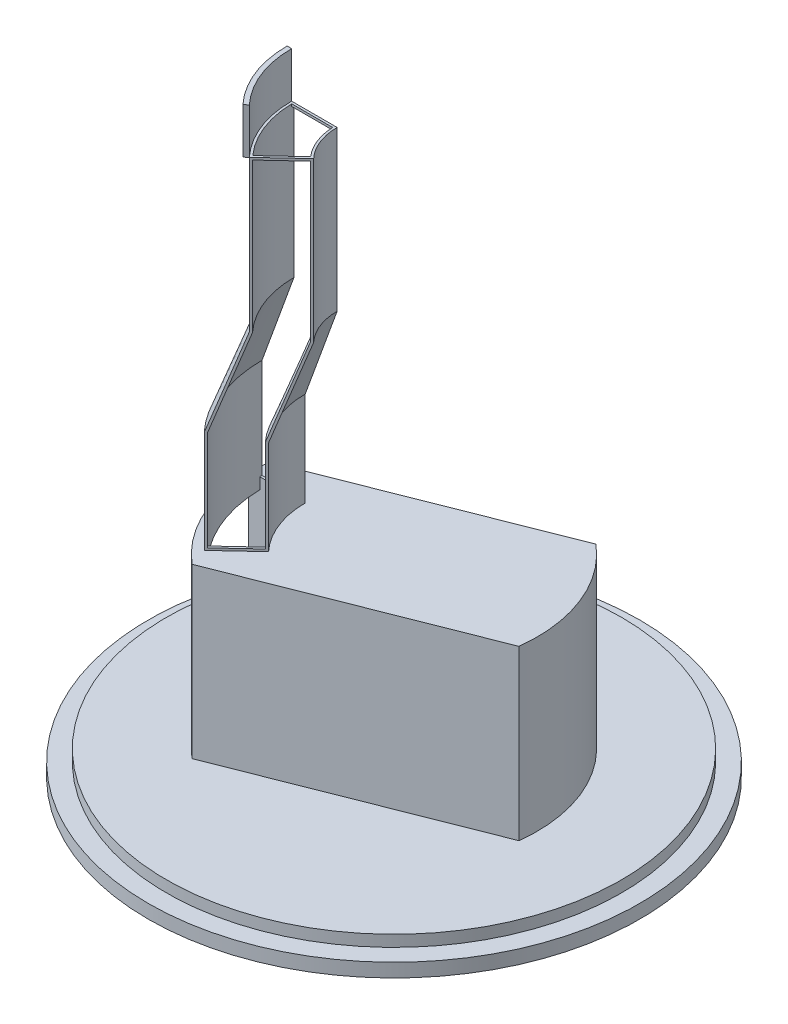
SolidWorks part; units mm, degrees
note: The reader was unsure of these and kept them because the rebuilt part matched: shared geometry of "3DSketch3<2>".
ref_plane "Front Plane" through (0, 0, 0) normal (0, 0, 1) x (1, 0, 0)
ref_plane "Top Plane" through (0, 0, 0) normal (0, 1, 0) x (1, 0, 0)
ref_plane "Right Plane" through (0, 0, 0) normal (1, 0, 0) x (0, 0, -1)
sketch "Sketch1" plane through (0, 0, 0) normal (0, 0, 1) x (1, 0, 0)
  line L0 (0, 0) -> (0, 18.0271) construction
  line L1 (-25, 0) -> (-45, 0)
  line L2 (-45, 0) -> (-45, -66.4735)
  line L3 (-45, -66.4735) -> (-59.0225, -105)
  line L4 (-59.0225, -105) -> (-59.0225, -150)
  line L5 (-59.0225, -150) -> (-39.0225, -150)
  line L6 (-39.0225, -150) -> (-39.0225, -108.5265)
  line L7 (-39.0225, -108.5265) -> (-25, -70)
  line L8 (-25, -70) -> (-25, 0)
  line L9 (-44, -1) -> (-44, -66.6498)
  line L10 (-44, -66.6498) -> (-58.0225, -105.1763)
  line L11 (-58.0225, -105.1763) -> (-58.0225, -149)
  line L12 (-58.0225, -149) -> (-40.0225, -149)
  line L13 (-40.0225, -149) -> (-40.0225, -108.3502)
  line L14 (-40.0225, -108.3502) -> (-26, -69.8237)
  line L15 (-26, -69.8237) -> (-26, -1)
  line L16 (-26, -1) -> (-44, -1)
  point P6 (-52.0113, -85.7367)
  dimension "D1" = 20
  dimension "D2" = 20
  dimension "D3" = 150
  dimension "D4" = 20
  dimension "D5" = 70
  dimension "D6" = 160
  dimension "D7" = 45
  dimension "D8" = 25
  dimension "D9" = 1
revolve "Revolve2" add sketch "Sketch1" angle 43 about L0
sketch3d "3DSketch2"
  line L0 (-25.9808, 0, 1) -> (-43.9886, 0, 1)
  line L1 (-19.6831, 0, 16.9875) -> (-32.8532, 0, 29.2688)
  line L2 (-25.9808, 0, 1) -> (-43.9886, 0, 1)
  line L3 (-19.6831, 0, 16.9875) -> (-32.8532, 0, 29.2688)
  arc A0 (-19.6831, 0, 16.9875) -> (-25.9808, 0, 1) centre (0, 0, 0) ccw
  arc A1 (-32.8532, 0, 29.2688) -> (-43.9886, 0, 1) centre (0, 0, 0) ccw
  arc A2 (-19.6831, 0, 16.9875) -> (-25.9808, 0, 1) centre (0, 0, 0) ccw
  arc A3 (-32.8532, 0, 29.2688) -> (-43.9886, 0, 1) centre (0, 0, 0) ccw
  point P3 (0, -26, 0)
  point P7 (0, -44, 0)
  point P8 (0, -26, 0)
  point P9 (0, -44, 0)
  dimension "D1" = 1
extrude "Cut-Extrude3" cut sketch "3DSketch2" along a picked direction on the side against the normal blind 3 contours A2 L2 A3 L3
sketch3d "3DSketch3"
  line L0 (-58.0139, -150, 1) -> (-40.01, -150, 1)
  line L1 (-43.1107, -150, 38.834) -> (-29.9435, -150, 26.5554)
  line L2 (-58.0139, -150, 1) -> (-40.01, -150, 1)
  line L3 (-43.1107, -150, 38.834) -> (-29.9435, -150, 26.5554)
  arc A0 (-43.1107, -150, 38.834) -> (-58.0139, -150, 1) centre (0, -150, 0) ccw
  arc A1 (-29.9435, -150, 26.5554) -> (-40.01, -150, 1) centre (0, -150, 0) ccw
  arc A2 (-43.1107, -150, 38.834) -> (-58.0139, -150, 1) centre (0, -150, 0) ccw
  arc A3 (-29.9435, -150, 26.5554) -> (-40.01, -150, 1) centre (0, -150, 0) ccw
  point P3 (0, -208.0225, 0)
  point P7 (0, -190.0225, 0)
  point P8 (0, -208.0225, 0)
  point P9 (0, -190.0225, 0)
  dimension "D1" = 1
extrude "Cut-Extrude4" cut sketch "3DSketch3" along a picked direction on the side against the normal blind 7
sketch "Sketch5" plane through (0, 0, 0) normal (0, 1, 0) x (1, 0, 0)
  line L0 (-45, 0) -> (-47, 0)
  line L1 (-32.9109, -30.6899) -> (-34.3736, -32.0539)
  line L2 (-32.9109, -30.6899) -> (-43.1663, -40.2533) construction
  arc A0 (-45, 0) -> (-32.9109, -30.6899) centre (0, 0) ccw
  arc A1 (-47, 0) -> (-34.3736, -32.0539) centre (0, 0) ccw
  dimension "D1" = 47
extrude "Boss-Extrude1" add sketch "Sketch5" along normal blind 20 separate body
sketch "Sketch6" plane through (0, -150, 0) normal (0, -1, 0) x (1, 0, 0)
  circle A0 centre (0, 0) radius 63
  dimension "D1" = 126
extrude "Boss-Extrude2" add sketch "Sketch6" along normal blind 4
extrude "Cut-Extrude5" cut sketch "3DSketch3<2>" along direction (0, -1, 0) on the side of the normal up to surface (4 mm away)
sketch3d "3DSketch3<2>" same geometry as "3DSketch3"
sketch "Sketch7" plane through (0, -154, 0) normal (0, -1, 0) x (-1, 0, 0)
  line L0 (43.1107, -38.834) -> (17.089, -15.3937) construction
  line L1 (58.0139, -1) -> (22.9783, -1) construction
  line L2 (17.089, -15.3937) -> (46.8089, -42.1654)
  line L3 (22.9783, -1) -> (62.9921, -1)
  arc A0 (17.089, -15.3937) -> (22.9783, -1) centre (0, 0) ccw
  circle A1 centre (0, 0) radius 63 construction
  circle A3 centre (0, 0) radius 63
  arc A4 (62.9921, -1) -> (46.8089, -42.1654) centre (0, 0) ccw
  dimension "D1" = 46
  dimension "D2" = 0
extrude "Boss-Extrude3" add sketch "Sketch7" along normal blind 70
sketch "Sketch10" plane through (0, -224, 0) normal (0, -1, 0) x (-1, 0, 0)
  circle A0 centre (0, 0) radius 100
  dimension "D1" = 200
extrude "Boss-Extrude4" add sketch "Sketch10" along normal blind 5
sketch "Sketch11" plane through (0, -229, 0) normal (0, -1, 0) x (-1, 0, 0)
  circle A0 centre (0, 0) radius 108
  dimension "D1" = 216
extrude "Boss-Extrude6" add sketch "Sketch11" along normal blind 6
sketch "Sketch14" plane through (0, -150, 0) normal (0, 1, 0) x (1, 0, 0)
  line L0 (0, 0) -> (-58.6163, -23.0896) construction
  line L1 (0, 0) -> (-64.4401, 0) construction
  line L2 (0, 0) -> (-44.4287, -41.4304) construction
  line L3 (-62.5388, 7.6089) -> (40.5488, 48.2162)
  line L4 (-40.5488, -48.2162) -> (62.5388, -7.6089)
  circle A0 centre (0, 0) radius 63 construction
  circle A1 centre (0, 0) radius 63
  circle M11 centre (0, 0) radius 63
  dimension "D4" = 126
  dimension "D1" = 21.5
  dimension "D2" = 21.5
  dimension "D3" = 30
  dimension "D5" = 30
  dimension "D6" = 60
extrude "Cut-Extrude6" cut sketch "Sketch14" against normal up to surface (74 mm away) contours L3 M11 | L4 M11 up to face at (0, -224, -100)
